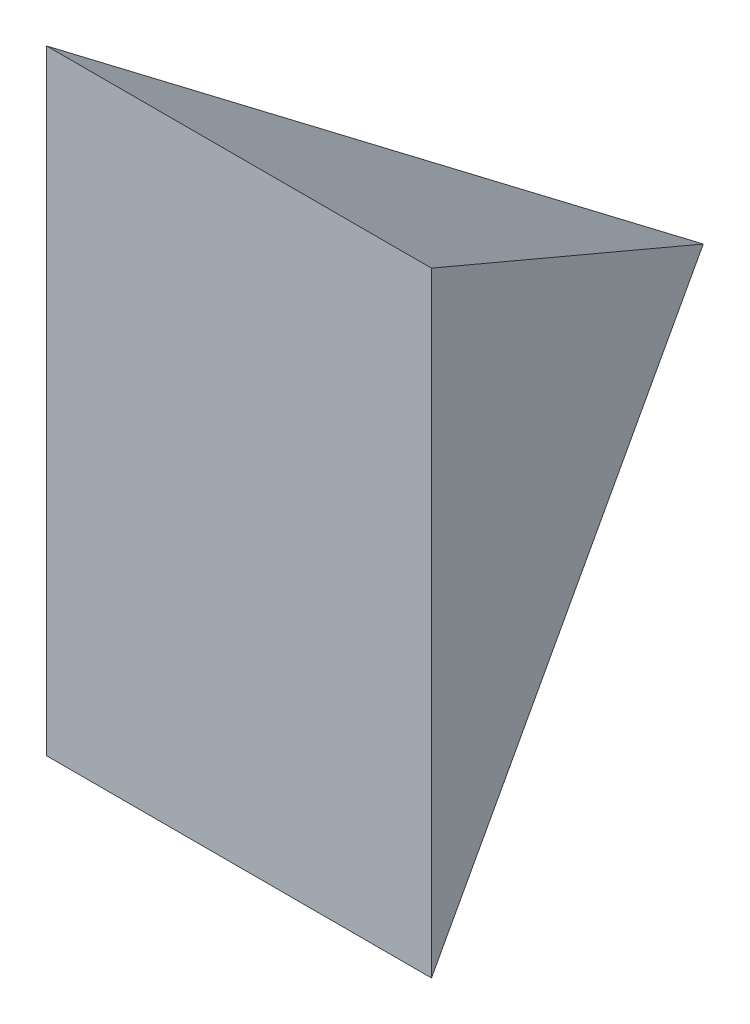
SolidWorks part; units mm, degrees
ref_plane "Plan de face" through (0, 0, 0) normal (0, 0, 1) x (1, 0, 0)
ref_plane "Plan de dessus" through (0, 0, 0) normal (0, 1, 0) x (1, 0, 0)
ref_plane "Plan de droite" through (0, 0, 0) normal (1, 0, 0) x (0, 0, -1)
sketch "Esquisse1" plane through (0, 0, 0) normal (0, 0, 1) x (1, 0, 0)
  point P0 (0, 0)
ref_plane "Plan1" through (0, 0, 450) normal (0, 0, 1) x (1, 0, 0)
sketch "Esquisse2" plane through (0, 0, 450) normal (0, 0, 1) x (1, 0, 0)
  line L1 (-186.5, 298) -> (186.5, 298)
  line L2 (-186.5, 298) -> (-186.5, -298)
  line L3 (-186.5, -298) -> (186.5, -298)
  line L4 (186.5, 298) -> (186.5, -298)
  line L5 (-186.5, 298) -> (186.5, -298) construction
  line L6 (-186.5, -298) -> (186.5, 298) construction
  point P0 (0, 0)
  dimension "D1" = 596
  dimension "D2" = 373
loft "Lissage1" add profiles "Esquisse1", "Esquisse2"
ref_point "Point1"
ref_axis "Axe1" through (0, 0, -376.2979) along (0, 0, 1)
ref_point "Point2"
